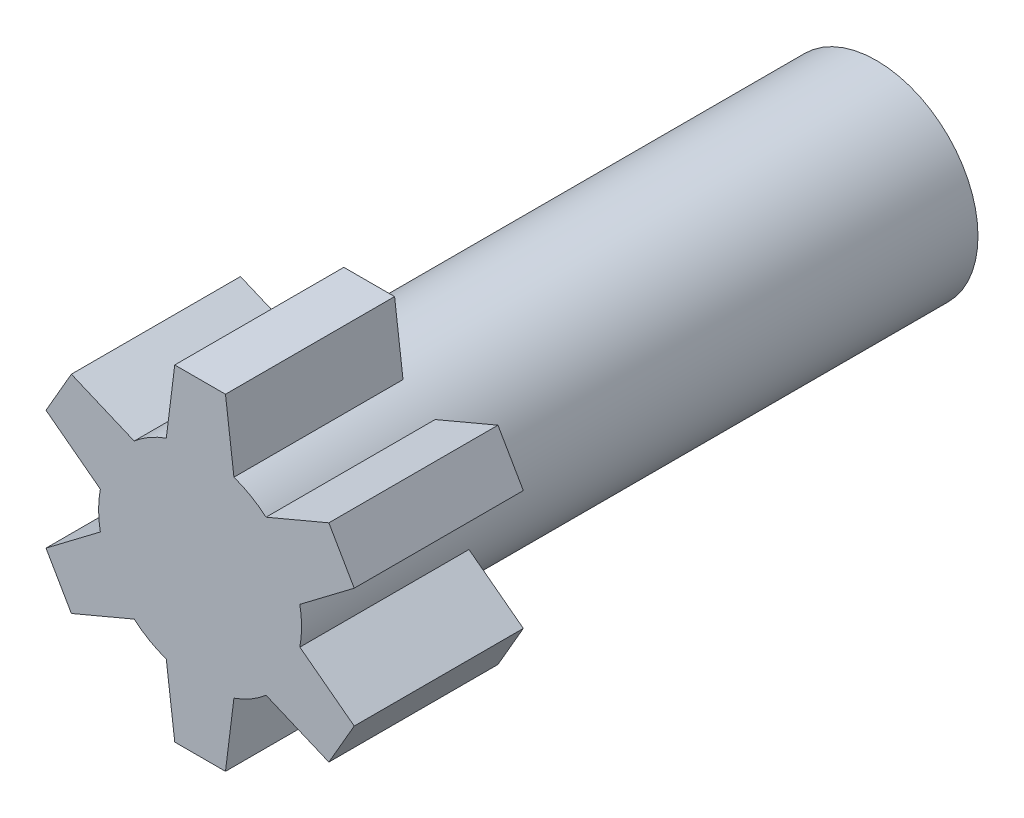
SolidWorks part; units mm, degrees
ref_plane "Front Plane" through (0, 0, 0) normal (0, 0, 1) x (1, 0, 0)
ref_plane "Top Plane" through (0, 0, 0) normal (0, 1, 0) x (1, 0, 0)
ref_plane "Right Plane" through (0, 0, 0) normal (1, 0, 0) x (0, 0, -1)
sketch "Esquisse1" plane through (0, 0, 0) normal (0, 0, 1) x (1, 0, 0)
  circle A0 centre (0, 0) radius 3
  dimension "D1" = 6
extrude "Main Extrusion" add sketch "Esquisse1" along normal blind 5
sketch "Esquisse2" plane through (0, 0, 5) normal (0, 0, 1) x (1, 0, 0)
  line L0 (-1, 2.8284) -> (1, 2.8284)
  line L1 (1, 2.8284) -> (0.75, 4.8284)
  line L2 (0.75, 4.8284) -> (-0.75, 4.8284)
  line L3 (-0.75, 4.8284) -> (-1, 2.8284)
  circle A0 centre (0, 0) radius 3 construction
  point P3 (0, 2.8284)
  dimension "D1" = 2
  dimension "D2" = 1.5
  dimension "D3" = 2
extrude "Gear Element" add sketch "Esquisse2" against normal up to surface (5 mm away) up to face at (3, 0, 0)
ref_axis "Axe1" through (0, 0, -0.5) along (0, 0, 1)
pattern_circular "Répétition circulaire1" count 6 every 60 about axis through (0, 0, -0.5) along (0, 0, 1) of "Gear Element"
sketch "Esquisse3" plane through (0, 0, 0) normal (0, 0, -1) x (-1, 0, 0)
  circle A0 centre (0, 0) radius 3
  dimension "D1" = 6
extrude "Main Axe" add sketch "Esquisse3" along normal blind 15
sketch "Esquisse4" plane through (0, 0, -15) normal (0, 0, -1) x (-1, 0, 0)
  line L1 (-2, 0.5) -> (2, 0.5)
  line L2 (-2, 0.5) -> (-2, -0.5)
  line L3 (-2, -0.5) -> (2, -0.5)
  line L4 (2, 0.5) -> (2, -0.5)
  point P4 (-2, 0)
  point P7 (0, 0.5)
  dimension "D1" = 1
  dimension "D2" = 4
extrude "Axe Trait" cut sketch "Esquisse4" against normal blind 3
